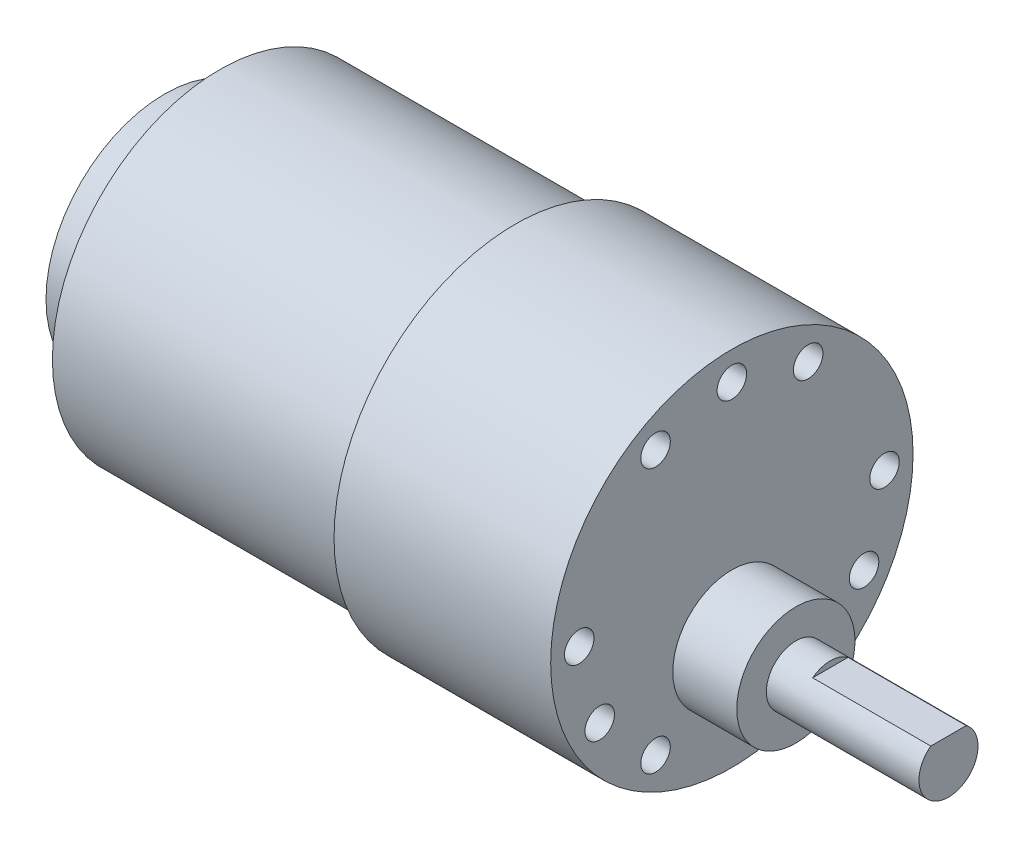
SolidWorks part; units mm, degrees
ref_plane "Plan de face" through (0, 0, 0) normal (0, 0, 1) x (1, 0, 0)
ref_plane "Plan de dessus" through (0, 0, 0) normal (0, 1, 0) x (1, 0, 0)
ref_plane "Plan de droite" through (0, 0, 0) normal (1, 0, 0) x (0, 0, -1)
sketch "Esquisse1" plane through (0, 0, 0) normal (0, 0, 1) x (1, 0, 0)
  line L0 (-59.1178, 0) -> (100.9551, 0) construction
  line L1 (-30, 0) -> (-30, 17)
  line L2 (-30, 17) -> (0, 17)
  line L3 (0, 17) -> (0, 18.4)
  line L4 (0, 18.4) -> (22, 18.4)
  line L5 (22, 18.4) -> (22, 0)
  line L10 (22, 0) -> (-30, 0)
  dimension "D1" = 17
  dimension "D2" = 18.4
  dimension "D3" = 30
  dimension "D4" = 22
revolve "Révolution1" add sketch "Esquisse1" angle 360 about L0
sketch "Esquisse3" plane through (0, 0, 0) normal (0, 0, 1) x (1, 0, 0)
  line L0 (8.4107, -7) -> (59.4134, -7) construction
  line L3 (22, -1) -> (28.5, -1)
  line L4 (28.5, -1) -> (28.5, -4)
  line L5 (28.5, -4) -> (44, -4)
  line L6 (44, -4) -> (44, -7)
  line L7 (44, -7) -> (22, -7)
  line L8 (22, -7) -> (22, -1)
  line L9 (22, -18.4) -> (22, 18.4) construction
  line L10 (31.7212, 0) -> (-32.2671, 0) construction
  dimension "D1" = 0
  dimension "D2" = 6.5
  dimension "D3" = 15.5
  dimension "D4" = 6
  dimension "D5" = 3
  dimension "D6" = 7
revolve "Révolution2" add sketch "Esquisse3" angle 360 about L0
sketch "Esquisse4" plane through (0, 0, 0) normal (0, 0, 1) x (1, 0, 0)
  line L0 (8.4107, -7) -> (59.4134, -7) construction
  line L1 (32, 6.8702) -> (50.6568, 6.8702)
  line L2 (32, 6.8702) -> (32, -4.6)
  line L3 (32, -4.6) -> (50.6568, -4.6)
  line L4 (50.6568, 6.8702) -> (50.6568, -4.6)
  line L5 (28.5, -1) -> (28.5, -4) construction
  dimension "D1" = 2.4
  dimension "D2" = 3.5
extrude "Enlèv. mat.-Extru.1" cut sketch "Esquisse4" against normal blind 10 and the other way blind 10
sketch "Esquisse5" plane through (-30, 0, 0) normal (-1, 0, 0) x (0, 0, 1)
  circle A0 centre (0, 0) radius 12.05
  circle A1 centre (0, 0) radius 11.9
  dimension "D1" = 24.1
  dimension "D2" = 23.8
extrude "Boss.-Extru.1" add sketch "Esquisse5" along normal blind 5.6
sketch "Esquisse6" plane through (22, 0, 0) normal (1, 0, 0) x (0, 0, -1)
  line L0 (0, 0) -> (-7.75, 13.4234) construction
  line L1 (0, 15.5) -> (0, 0) construction
  line L2 (0, 0) -> (7.75, 13.4234) construction
  circle A0 centre (0, 15.5) radius 1.5
  circle A1 centre (0, 0) radius 15.5 construction
  circle A2 centre (7.75, 13.4234) radius 1.5
  circle A3 centre (-7.75, 13.4234) radius 1.5
  dimension "D1" = 3
  dimension "D5" = 3
  dimension "D6" = 3
  dimension "D2" = 15.5
  dimension "D3" = 30
  dimension "D4" = 30
extrude "Enlèv. mat.-Extru.2" cut sketch "Esquisse6" against normal blind 5
pattern_circular "Répétition circulaire1" count 3 over 360 about axis through (22, 0, 0) along (-1, 0, 0) of "Enlèv. mat.-Extru.2"
